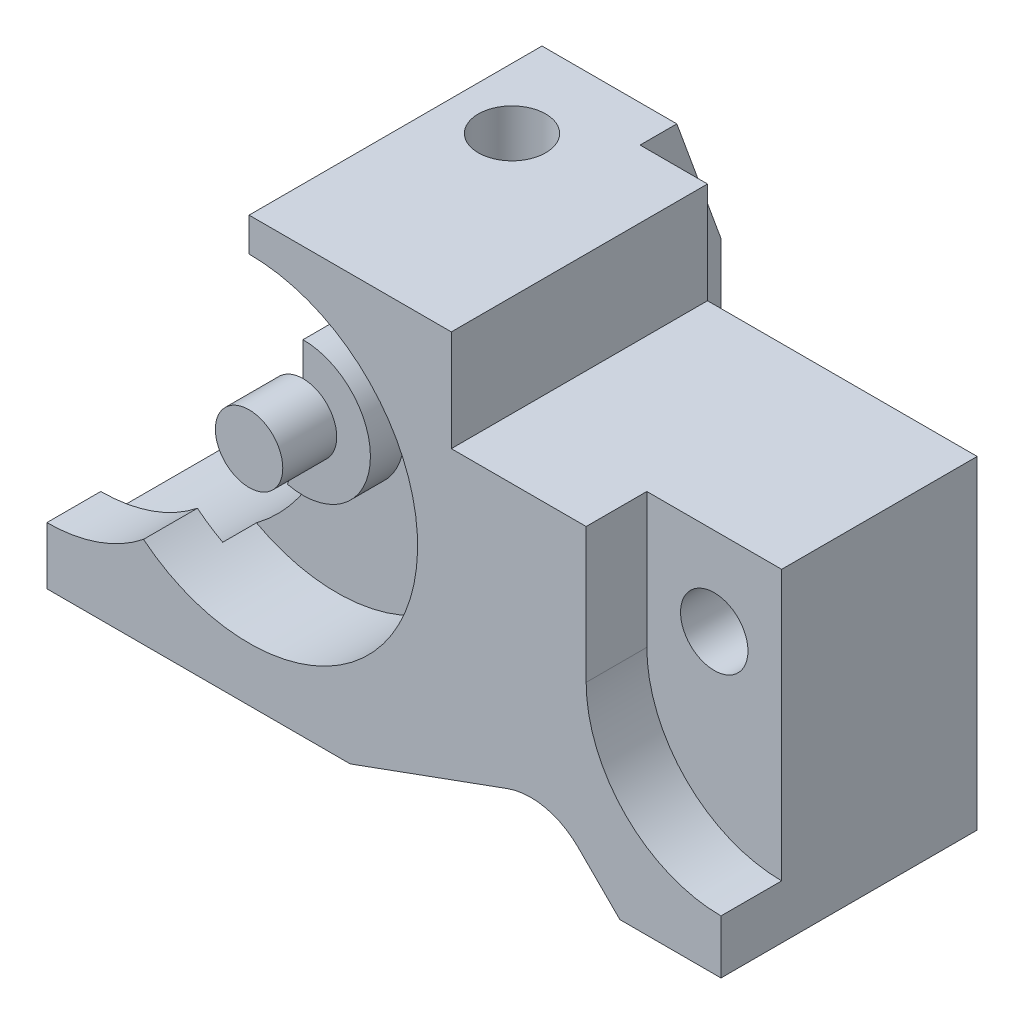
SolidWorks part; units mm, degrees
note: The reader was unsure of these and kept them because the rebuilt part matched: shared geometry of "Sketch2<5>".
ref_plane "Front Plane" through (0, 0, 0) normal (0, 0, 1) x (1, 0, 0)
ref_plane "Top Plane" through (0, 0, 0) normal (0, 1, 0) x (1, 0, 0)
ref_plane "Right Plane" through (0, 0, 0) normal (1, 0, 0) x (0, 0, -1)
sketch "Sketch1" plane through (0, 0, 0) normal (0, 0, 1) x (1, 0, 0)
  line L0 (10, 31.5) -> (10, 16.5)
  line L1 (50, -31.5) -> (-50, -31.5)
  line L2 (50, -31.5) -> (50, 31.5)
  line L3 (50, 31.5) -> (-50, 31.5)
  line L4 (-50, -31.5) -> (-50, 31.5)
  line L5 (50, -31.5) -> (-50, 31.5) construction
  line L6 (50, 31.5) -> (-50, -31.5) construction
  line L7 (10, 16.5) -> (50, 16.5)
  line L8 (-5, -31.5) -> (18.3397, -23.0051)
  line L9 (28.8309, -25.3309) -> (35, -31.5)
  arc A1 (28.8309, -25.3309) -> (18.3397, -23.0051) centre (21.7599, -32.402) ccw
  point P0 (0, 0)
  point P14 (37.7042, -31.5)
  dimension "D4" = 15
  dimension "D5" = 40
  dimension "D6" = 10
  dimension "D7" = 20
  dimension "D9" = 15
  dimension "D1" = 63
  dimension "D2" = 100
  dimension "D3" = 40
  dimension "D8" = 45
extrude "Boss-Extrude2" add sketch "Sketch1" along normal blind 50 contours A1 L9 L1 L2 L7 L0 L3 L4 L8
sketch "Sketch2" plane through (0, 0, 50) normal (0, 0, 1) x (1, 0, 0)
  line L0 (50, -31.5) -> (35, -31.5) construction
  line L1 (30, 16.5) -> (30, -3.523)
  line L3 (10, 16.5) -> (50, 16.5) construction
  line L5 (50, -31.5) -> (50, 16.5) construction
  circle A0 centre (40, 3.5) radius 5
  arc A1 (30, -3.523) -> (50, -23.523) centre (50, -3.523) ccw
  point P12 (50, -23.523)
  line M6 (50, -31.5) -> (50, 16.5)
  line M7 (50, 16.5) -> (10, 16.5)
  dimension "D1" = 10
  dimension "D3" = 20
  dimension "D5" = 27.977
  dimension "D2" = 35
  dimension "D4" = 10
sketch "Sketch13" plane through (0, 0, 50) normal (0, 0, 1) x (1, 0, 0)
extrude "Cut-Extrude1" cut sketch "Sketch2" against normal through all contours A0
sketch "Sketch14" plane through (0, 0, 50) normal (0, 0, 1) x (1, 0, 0)
extrude "Cut-Extrude2" cut sketch "Sketch2<5>" against normal blind 9 contours L1 A1 A0 M6 M7
sketch "Sketch2<5>" plane through (0, 0, 50) normal (0, 0, 1) x (1, 0, 0) same geometry as "Sketch2"
sketch "Sketch15" plane through (0, 0, 50) normal (0, 0, 1) x (1, 0, 0)
  line L2 (-50, -31.5) -> (-50, 31.5) construction
  line L4 (10, 31.5) -> (-50, 31.5) construction
  line L5 (-20, 31.5) -> (-20, 1.5)
  circle A3 centre (-20, 1.5) radius 30 construction
  circle A4 centre (-20, 1.5) radius 25
  arc A6 (-20, 1.5) -> (-32.4589, -20.1743) centre (-49.8733, 4.2539) cw
  point P15 (0, 0)
  point P19 (-35.5446, -18.0797)
  dimension "D2" = 50
  dimension "D3" = 30
  dimension "D4" = 49.8733
  dimension "D1" = 60
sketch "Sketch17" plane through (0, 0, 50) normal (0, 0, 1) x (1, 0, 0)
sketch "Sketch28" plane through (0, 0, 50) normal (0, 0, 1) x (1, 0, 0)
sketch "Sketch30" plane through (0, 0, 0) normal (0, 0, -1) x (-1, 0, 0)
  line L0 (50, -31.5) -> (50, 31.5) construction
  line L2 (20, 31.5) -> (20, 1.5) construction
  line L3 (20, 1.5) -> (20, 31.5)
  arc A0 (50, -26.5) -> (20, 1.5) centre (49.9333, 3.4999) cw
  point P3 (49.9333, -26.5)
  point P10 (20, 31.5)
  dimension "D1" = 5
  dimension "D2" = 30
extrude "Cut-Extrude12" cut sketch "Sketch30" against normal blind 42 and the other way through all flip side to cut
sketch "Sketch36" plane through (0, 0, 0) normal (0, 0, -1) x (-1, 0, 0)
extrude "Cut-Extrude14" cut sketch "Sketch15" against normal blind 42 contours A6 L5 A4
sketch "Sketch39" plane through (0, 0, 50) normal (0, 0, 1) x (1, 0, 0)
  line L0 (-50, -23) -> (-50, 31.5)
  line L1 (-50, -31.5) -> (-50, 31.5) construction
  line L2 (-20, 26.5) -> (-20, 31.5)
  line L3 (10, 31.5) -> (-50, 31.5) construction
  line L4 (-50, 31.5) -> (-20, 31.5)
  arc A0 (-50, -23) -> (-35.6633, -17.9849) centre (-50, 0) ccw
  arc A1 (-20, 26.5) -> (-32.4589, -20.1743) centre (-20, 1.5) ccw construction
  dimension "D1" = 23
extrude "Cut-Extrude16" cut sketch "Sketch39" against normal through all and the other way through all
sketch "Sketch41" plane through (0, 0, 50) normal (0, 0, 1) x (1, 0, 0)
  circle A0 centre (-20, 1.5) radius 25
  dimension "D1" = 50
extrude "Cut-Extrude17" cut sketch "Sketch41" against normal blind 13
sketch "Sketch42" plane through (0, 0, 37) normal (0, 0, 1) x (1, 0, 0)
  line L0 (-20, 26.5) -> (-20, 1.5) construction
  line L2 (-20, 26.5) -> (-20, 1.5)
  line L3 (-20, 11.5) -> (-20, 1.5)
  arc A1 (-20, 11.5) -> (-22.3203, -8.2271) centre (-20, 1.5) cw
  arc A2 (-31.9085, -20.4815) -> (-20, 1.5) centre (-49.9333, 3.4999) ccw construction
  arc A5 (-31.9085, -20.4815) -> (-20, 1.5) centre (-49.9333, 3.4999) ccw
  arc A6 (-31.9085, -20.4815) -> (-20, 26.5) centre (-20, 1.5) ccw
  arc A7 (-22.3203, -8.2271) -> (-20, 1.5) centre (-49.9333, 3.4999) ccw
  dimension "D1" = 10
  dimension "D2" = 0
extrude "Boss-Extrude8" add sketch "Sketch42" along normal blind 5
sketch "Sketch43" plane through (0, 0, 42) normal (0, 0, 1) x (1, 0, 0)
  circle A0 centre (-20, 1.5) radius 5
extrude "Boss-Extrude9" add sketch "Sketch43" along normal blind 8
sketch "Sketch44" plane through (-20, 0, 0) normal (-1, 0, 0) x (0, 0, 1)
  line L0 (0, 13.5) -> (6.5515, 31.5)
  line L1 (0, 31.5) -> (0, 1.5) construction
  line L2 (0, 31.5) -> (50, 31.5) construction
  line L3 (0, 13.5) -> (0, 31.5)
  line L4 (0, 31.5) -> (6.5515, 31.5)
  dimension "D1" = 20
  dimension "D2" = 18
extrude "Cut-Extrude19" cut sketch "Sketch44" against normal through all
sketch "Sketch45" plane through (0, 16.5, 0) normal (0, 1, 0) x (1, 0, 0)
  line L0 (50, 0) -> (50, -12)
  line L1 (50, -41) -> (50, -1.0919) construction
  line L2 (50, -12) -> (0, -12)
  line L3 (0, -12) -> (0, 0)
  line L4 (0, 0) -> (50, 0)
  dimension "D1" = 12
  dimension "D2" = 50
  dimension "D3" = 12
  dimension "D4" = 90
extrude "Cut-Extrude21" cut sketch "Sketch45" against normal through all and the other way through all contours L4 L0 L2 L3
sketch "Sketch46" plane through (0, 31.5, 0) normal (0, 1, 0) x (1, 0, 0)
  line L0 (10, -50) -> (-20, -50) construction
  line L3 (-20, -6.5515) -> (-20, -50) construction
  circle A0 centre (-11, -20) radius 5
  point P6 (-20, -19.6901)
  dimension "D1" = 10
  dimension "D2" = 30
  dimension "D3" = 9
extrude "Cut-Extrude22" cut sketch "Sketch46" against normal through all contours A0
equation "\"A\"= 63mm"
equation "\"B\"= 50mm"
equation "\"C\"= 100mm"
